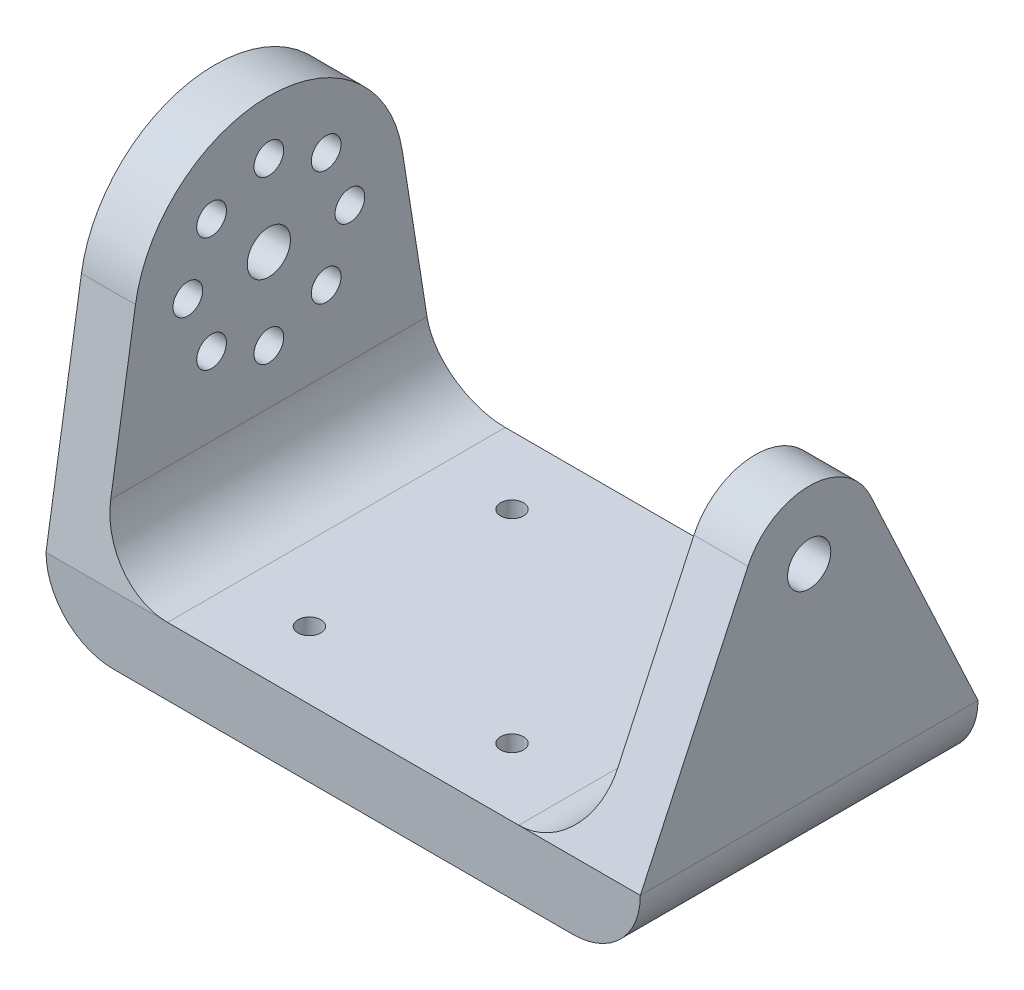
SolidWorks part; units mm, degrees
material "ABS"
ref_plane "正面" through (0, 0, 0) normal (0, 0, 1) x (1, 0, 0)
ref_plane "平面" through (0, 0, 0) normal (0, 1, 0) x (1, 0, 0)
ref_plane "右側面" through (0, 0, 0) normal (1, 0, 0) x (0, 0, -1)
sketch "ｽｹｯﾁ1" plane through (0, 0, 0) normal (0, 1, 0) x (1, 0, 0)
  line L1 (22, 0) -> (-22, 0)
  line L2 (22, 0) -> (22, 25)
  line L3 (22, 25) -> (-22, 25)
  line L4 (-22, 0) -> (-22, 25)
  dimension "D1" = 44
  dimension "D2" = 25
extrude "ﾎﾞｽ - 押し出し1" add sketch "ｽｹｯﾁ1" along normal blind 5
sketch "ｽｹｯﾁ2" plane through (-22, 0, 0) normal (-1, 0, 0) x (0, 0, 1)
  line L0 (-25, 5) -> (0, 5)
  line L1 (0, 5) -> (-2.6231, 21.5641)
  line L2 (-22.3769, 21.5641) -> (-25, 5)
  line L3 (-12.5, 5) -> (-12.5, 20) construction
  arc A0 (-2.6231, 21.5641) -> (-22.3769, 21.5641) centre (-12.5, 20) ccw
  circle A1 centre (-12.5, 20) radius 6 construction
  circle A2 centre (-12.5, 26) radius 1.1
  circle A3 centre (-8.2574, 24.2426) radius 1.1
  circle A4 centre (-6.5, 20) radius 1.1
  circle A5 centre (-8.2574, 15.7574) radius 1.1
  circle A6 centre (-12.5, 14) radius 1.1
  circle A7 centre (-16.7426, 15.7574) radius 1.1
  circle A8 centre (-18.5, 20) radius 1.1
  circle A9 centre (-16.7426, 24.2426) radius 1.1
  circle A10 centre (-12.5, 20) radius 1.6
  point P28 (-12.5, 20)
  dimension "D1" = 20
  dimension "D3" = 12
  dimension "D4" = 2.2
  dimension "D6" = 3.2
  dimension "D2" = 15
  dimension "D5" = 8
extrude "ﾎﾞｽ - 押し出し2" add sketch "ｽｹｯﾁ2" against normal blind 4
sketch "ｽｹｯﾁ3" plane through (22, 0, 0) normal (1, 0, 0) x (0, 0, -1)
  line L2 (25, 5) -> (0, 5) construction
  line L3 (0, 5) -> (7.9673, 22.1106)
  line L4 (17.0327, 22.1106) -> (25, 5)
  line L5 (25, 5) -> (0, 5)
  arc A1 (17.0327, 22.1106) -> (7.9673, 22.1106) centre (12.5, 20) ccw
  circle A2 centre (12.5, 20) radius 1.6
  circle A3 centre (12.5, 20) radius 1.6 construction
  dimension "D1" = 3.2
  dimension "D2" = 5
extrude "ﾎﾞｽ - 押し出し3" add sketch "ｽｹｯﾁ3" against normal blind 4
fillet "ﾌｨﾚｯﾄ1" radius 5 4 edges at (18, 5, -12.5) (-18, 5, -12.5) (22, 0, -12.5) (-22, 0, -12.5)
sketch "ｽｹｯﾁ4" plane through (0, 5, 0) normal (0, 1, 0) x (1, 0, 0)
  line L0 (0, 25) -> (0, 0) construction
  line L1 (13, 25) -> (-13, 25) construction
  line L2 (-13, 0) -> (13, 0) construction
  line L3 (-13, 12.5) -> (13, 12.5) construction
  line L4 (-13, 25) -> (-13, 0) construction
  line L5 (13, 0) -> (13, 25) construction
  line L7 (-7.5, 20) -> (7.5, 20) construction
  line L8 (-7.5, 20) -> (-7.5, 5) construction
  line L9 (-7.5, 5) -> (7.5, 5) construction
  line L10 (7.5, 20) -> (7.5, 5) construction
  line L11 (-7.5, 20) -> (7.5, 5) construction
  line L12 (-7.5, 5) -> (7.5, 20) construction
  circle A0 centre (-7.5, 20) radius 0.85
  circle A1 centre (7.5, 20) radius 0.85
  circle A2 centre (7.5, 5) radius 0.85
  circle A3 centre (-7.5, 5) radius 0.85
  point P12 (0, 12.5)
  dimension "D3" = 1.7
  dimension "D1" = 15
  dimension "D2" = 15
extrude "ｶｯﾄ - 押し出し1" cut sketch "ｽｹｯﾁ4" against normal blind 5
